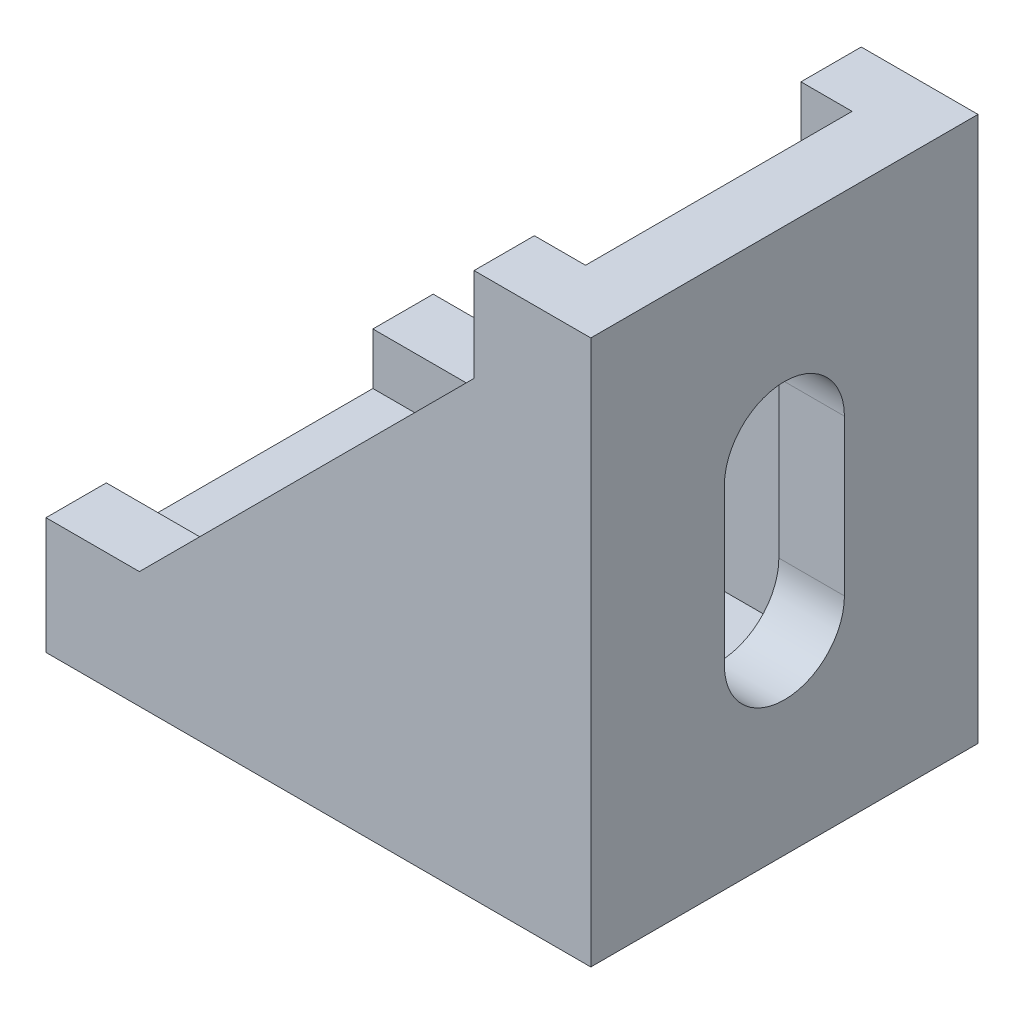
SolidWorks part; units mm, degrees
material "2024 合金"
ref_plane "前视基准面" through (0, 0, 0) normal (0, 0, 1) x (1, 0, 0)
ref_plane "上视基准面" through (0, 0, 0) normal (0, 1, 0) x (1, 0, 0)
ref_plane "右视基准面" through (0, 0, 0) normal (1, 0, 0) x (0, 0, -1)
sketch "草图1" plane through (0, 0, 0) normal (0, 1, 0) x (1, 0, 0)
  line L0 (-4, 0) -> (4, 0) construction
  line L1 (-14, 9.95) -> (14, 9.95)
  line L2 (-14, 9.95) -> (-14, -9.95)
  line L3 (-14, -9.95) -> (14, -9.95)
  line L4 (14, 9.95) -> (14, -9.95)
  line L5 (-14, 9.95) -> (14, -9.95) construction
  line L6 (-14, -9.95) -> (14, 9.95) construction
  line L7 (-4, 3.085) -> (4, 3.085)
  line L8 (-4, -3.085) -> (4, -3.085)
  arc A0 (-4, 3.085) -> (-4, -3.085) centre (-4, 0) ccw
  arc A1 (4, -3.085) -> (4, 3.085) centre (4, 0) ccw
  point P0 (0, 0)
  point P8 (0, 0)
  dimension "D4" = 8
  dimension "D1" = 28
  dimension "D2" = 19.9
  dimension "D3" = 6.17
extrude "凸台-拉伸1" add sketch "草图1" along normal blind 3.35
sketch "草图3" plane through (0, 0, 9.95) normal (0, 0, 1) x (1, 0, 0)
  line L0 (-14, 3.35) -> (-14, 0) construction
  line L1 (14, 0) -> (-14, 0)
  line L2 (14, 0) -> (14, 6)
  line L3 (14, 6) -> (-14, 6)
  line L4 (-14, 0) -> (-14, 6)
  line L5 (-9.2, 6) -> (8, 23.2)
  line L6 (14, 0) -> (8, 0)
  line L7 (14, 0) -> (14, 28)
  line L8 (14, 28) -> (8, 28)
  line L9 (8, 0) -> (8, 28)
  line M9 (-14, 0) -> (14, 0)
  line M10 (14, 0) -> (14, 3.35)
  line M11 (14, 3.35) -> (-14, 3.35)
  line M12 (-14, 3.35) -> (-14, 0)
  dimension "D1" = 28
  dimension "D2" = 6
  dimension "D3" = 6
  dimension "D4" = 4.8
  dimension "D5" = 4.8
extrude "凸台-拉伸2" add sketch "草图3" against normal blind 3.1 contours L9 L3 L7 L8 | L3 L9 L5 | L9 L3 L4 M11 | L9 M9 M11 M12 | L9 L2 L3 M11 | L9 L1 M10 M11 region at (11, 1.675, 9.95) region at (-3, 1.675, 9.95) region at (11, 4.675, 9.95) region at (-3, 4.675, 9.95) region at (11, 17, 9.95) region at (2.2667, 11.7333, 9.95)
extrude "凸台-拉伸3" add sketch "草图3<3>" against normal blind 3.1 from offset 16.8 contours L9 L3 L7 L8 | L9 L3 L4 M11 | L9 L2 L3 M11 | L9 L1 M10 M11 | L9 M9 M11 M12 | L3 L9 L5 region at (11, 1.675, 9.95) region at (-3, 1.675, 9.95) region at (11, 4.675, 9.95) region at (-3, 4.675, 9.95) region at (11, 17, 9.95) region at (2.2667, 11.7333, 9.95) offset against normal yes
sketch "草图3<3>" plane through (0, 0, 9.95) normal (0, 0, 1) x (1, 0, 0) same geometry as "草图3"
sketch "草图4" plane through (14, 0, 0) normal (1, 0, 0) x (0, 0, -1)
  line L0 (0, 28) -> (0, 0) construction
  line L1 (-9.95, 0) -> (9.95, 0)
  line L2 (-9.95, 0) -> (-9.95, 28)
  line L3 (-9.95, 28) -> (9.95, 28)
  line L4 (9.95, 0) -> (9.95, 28)
  line L5 (-9.95, 14) -> (9.95, 14) construction
  line L6 (0, 18) -> (0, 10) construction
  line L7 (3.085, 18) -> (3.085, 10)
  line L8 (-3.085, 18) -> (-3.085, 10)
  arc A0 (3.085, 18) -> (-3.085, 18) centre (0, 18) ccw
  arc A1 (-3.085, 10) -> (3.085, 10) centre (0, 10) ccw
  point P13 (0, 14)
  point P19 (0, 14)
  dimension "D1" = 6.17
  dimension "D2" = 8
extrude "凸台-拉伸4" add sketch "草图4" against normal blind 3.37
